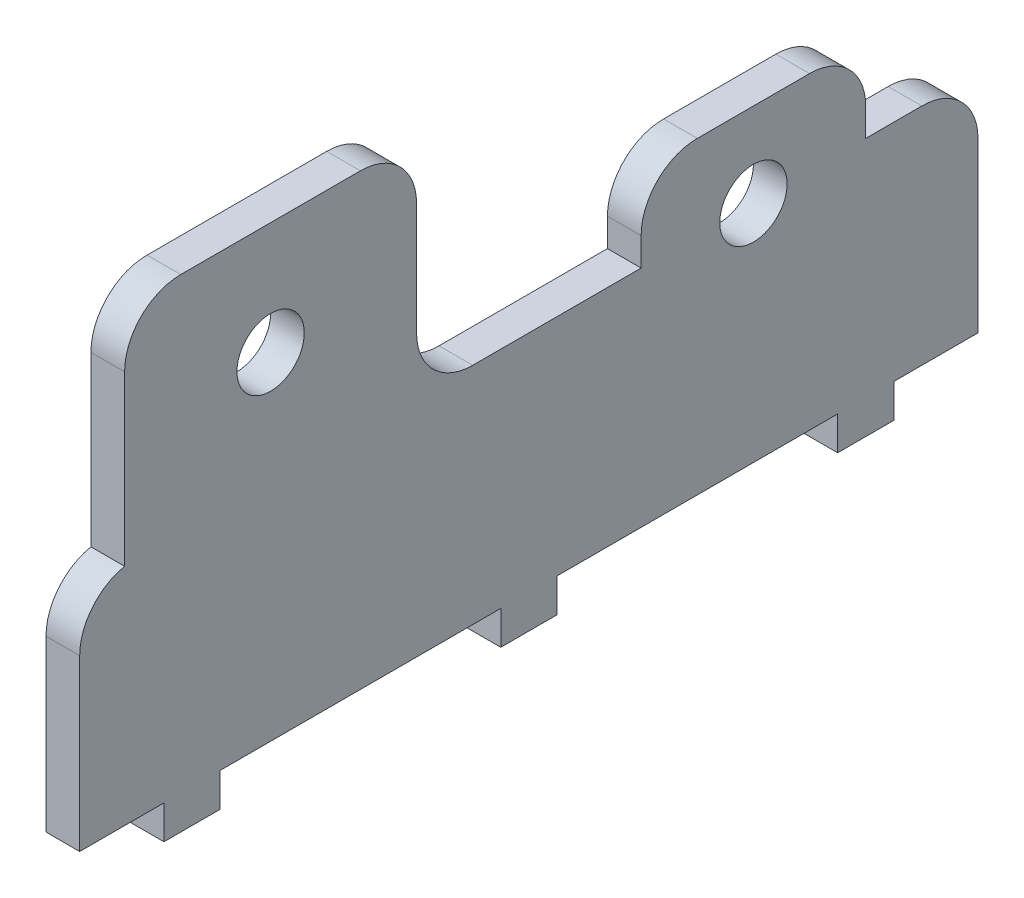
SolidWorks part; units mm, degrees
ref_plane "Front Plane" through (0, 0, 0) normal (0, 0, 1) x (1, 0, 0)
ref_plane "Top Plane" through (0, 0, 0) normal (0, 1, 0) x (1, 0, 0)
ref_plane "Right Plane" through (0, 0, 0) normal (1, 0, 0) x (0, 0, -1)
sketch "Sketch1" plane through (0, 0, 0) normal (1, 0, 0) x (0, 0, -1)
  line L1 (50, 0) -> (-30, 0)
  line L2 (50, 0) -> (50, 40)
  line L3 (50, 40) -> (-30, 40)
  line L4 (-30, 0) -> (-30, 40)
  line L5 (55, 0) -> (-55, 0) construction
  point P0 (0, 0)
  dimension "D2" = 30
  dimension "D1" = 80
  dimension "D4" = 40
extrude "Boss-Extrude1" add sketch "Sketch1" along normal blind 3
sketch "Sketch2" plane through (3, 0, 0) normal (1, 0, 0) x (0, 0, -1)
  line L0 (-30, 0) -> (50, 0) construction
  line L1 (50, 0) -> (50, 40) construction
  line L7 (-26.9862, 0) -> (-28.4862, -10) construction
  line L16 (1.65, 0) -> (-1.65, 0) construction
  line L18 (0, 40) -> (50, 40)
  line L19 (0, 40) -> (0, 27.5)
  line L20 (20, 27.5) -> (40, 27.5)
  line L21 (50, 40) -> (50, 27.5)
  line L22 (-30, 0) -> (50, 0) construction
  line L24 (50, 27.5) -> (50, 20)
  line L25 (50, 20) -> (40, 20)
  line L26 (40, 27.5) -> (40, 20)
  line L27 (50, 40) -> (-30, 40) construction
  line L29 (0, 27.5) -> (0, 20)
  line L30 (0, 20) -> (20, 20)
  line L31 (20, 27.5) -> (20, 20)
  line L32 (-26, 40) -> (-30, 40)
  line L33 (-26, 40) -> (-26, 20)
  line L34 (-26, 20) -> (-30, 20)
  line L35 (-30, 40) -> (-30, 20)
  line L36 (-30, 40) -> (-30, 0) construction
  circle A1 centre (30, 20) radius 3
  circle A8 centre (-13, 30) radius 3
  point P6 (-28.4862, -10)
  point P11 (28.0724, -10)
  dimension "D1" = 6
  dimension "D3" = 20
  dimension "D4" = 6
  dimension "D6" = 20
  dimension "D7" = 30
  dimension "D11" = 10
  dimension "D12" = 13
  dimension "D2" = 30
  dimension "D5" = 43
  dimension "D8" = 7.5
  dimension "D9" = 20
  dimension "D10" = 10
extrude "Cut-Extrude1" cut sketch "Sketch2" against normal through all
fillet "Fillet2" radius 5 7 edges at (1.5, 40, 0) (1.5, 20, -50) (1.5, 27.5, -40) (1.5, 27.5, -20) (1.5, 20, 0) (1.5, 20, 30) (1.5, 40, 26)
sketch "Sketch3" plane through (0, 0, 0) normal (0, -1, 0) x (1, 0, 0)
  line L0 (3, 30) -> (3, -50) construction
  line L1 (3, -42.5) -> (0, -42.5)
  line L2 (3, -42.5) -> (3, -37.5)
  line L3 (3, -37.5) -> (0, -37.5)
  line L4 (0, -42.5) -> (0, -37.5)
  line L5 (0, 30) -> (0, -50) construction
  line L6 (3, -50) -> (0, -50) construction
  dimension "D1" = 5
  dimension "D2" = 7.5
extrude "Boss-Extrude2" add sketch "Sketch3" along normal blind 3
pattern_linear "LPattern1" count 3 spacing 30 along (0, 0, 1) of "Boss-Extrude2"
